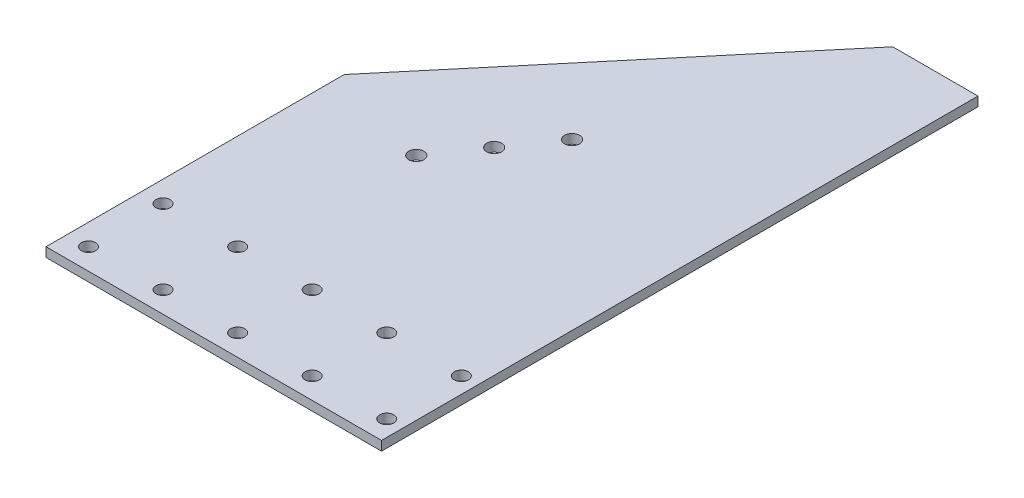
SolidWorks part; units mm, degrees
material "6061-T6 (SS)"
ref_plane "Front Plane" through (0, 0, 0) normal (0, 0, 1) x (1, 0, 0)
ref_plane "Top Plane" through (0, 0, 0) normal (0, 1, 0) x (1, 0, 0)
ref_plane "Right Plane" through (0, 0, 0) normal (1, 0, 0) x (0, 0, -1)
sketch "Sketch1" plane through (0, 0, 0) normal (0, 1, 0) x (1, 0, 0)
  line L5 (0, 0) -> (114.3, 0)
  line L6 (0, 0) -> (0, 203.2)
  line L7 (0, 203.2) -> (114.3, 203.2)
  line L8 (114.3, 0) -> (114.3, 203.2)
  dimension "D1" = 203.2
  dimension "D2" = 114.3
extrude "Boss-Extrude1" add sketch "Sketch1" along normal blind 3.175
sketch "Sketch2" plane through (0, 3.175, 0) normal (0, 1, 0) x (1, 0, 0)
  line L0 (0, 0) -> (114.3, 0) construction
  line L1 (0, 203.2) -> (0, 0) construction
  line L2 (114.3, 0) -> (114.3, 203.2) construction
  line L5 (-1.7463, 0) -> (1.7463, 0) construction
  circle A0 centre (7.239, 7.239) radius 2.413
  circle A2 centre (7.239, 32.639) radius 2.413
  circle A3 centre (32.639, 32.639) radius 2.413
  circle A4 centre (58.039, 32.639) radius 2.413
  circle A5 centre (83.439, 32.639) radius 2.413
  circle A6 centre (108.839, 32.639) radius 2.413
  circle A7 centre (32.639, 7.239) radius 2.413
  circle A8 centre (58.039, 7.239) radius 2.413
  circle A9 centre (83.439, 7.239) radius 2.413
  circle A10 centre (108.839, 7.239) radius 2.413
  dimension "D1" = 4.826
  dimension "D2" = 7.239
  dimension "D3" = 7.239
  dimension "D6" = 25.4
  dimension "D7" = 7.239
  dimension "D8" = 5.461
  dimension "D4" = 2
  dimension "D5" = 5
extrude "Cut-Extrude1" cut sketch "Sketch2" against normal through all
sketch "Sketch3" plane through (0, 3.175, 0) normal (0, 1, 0) x (1, 0, 0)
  circle A0 centre (57.9964, 121.2022) radius 2.5527
  circle A4 centre (47.0698, 105.5974) radius 2.5527
  circle A6 centre (36.1431, 89.9925) radius 2.5527
  dimension "D1" = 5.1054
  dimension "D4" = 19.05
  dimension "D3" = 3
extrude "Cut-Extrude2" cut sketch "Sketch3" against normal through all
sketch "Sketch5" plane through (0, 0, 0) normal (0, -1, 0) x (-1, 0, 0)
  line L0 (-85.2525, 203.2) -> (0, 101.6)
  line L1 (-114.3, 203.2) -> (0, 203.2) construction
  line L2 (0, 203.2) -> (0, 0) construction
  line L3 (0, 101.6) -> (0, 203.2)
  line L4 (0, 203.2) -> (-85.2525, 203.2)
  dimension "D1" = 50
extrude "Cut-Extrude4" cut sketch "Sketch5" against normal through all
